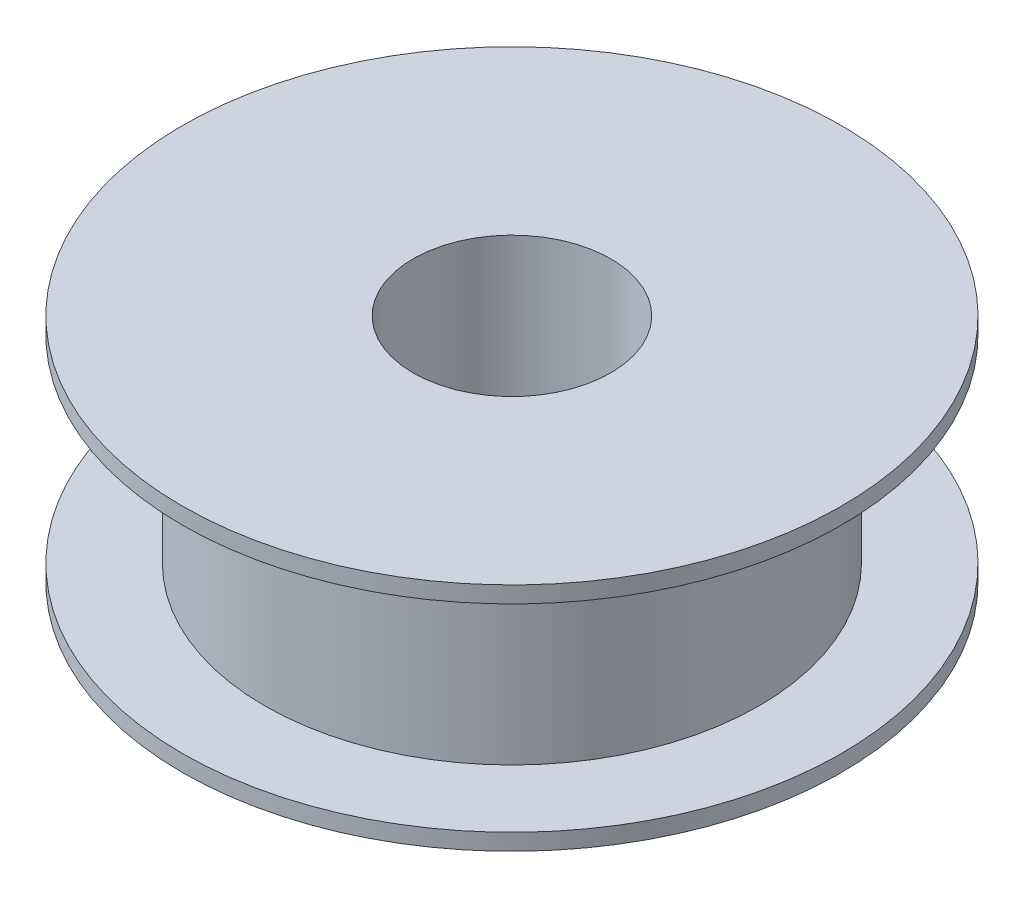
SolidWorks part; units mm, degrees
ref_plane "Plan de face" through (0, 0, 0) normal (0, 0, 1) x (1, 0, 0)
ref_plane "Plan de dessus" through (0, 0, 0) normal (0, 1, 0) x (1, 0, 0)
ref_plane "Plan de droite" through (0, 0, 0) normal (1, 0, 0) x (0, 0, -1)
sketch "Esquisse1" plane through (0, 0, 0) normal (0, 1, 0) x (1, 0, 0)
  circle A0 centre (0, 0) radius 15
  circle A1 centre (0, 0) radius 20
  circle A2 centre (0, 0) radius 6
  dimension "D1" = 5
  dimension "D2" = 30
  dimension "D3" = 12
extrude "Boss.-Extru.1" add sketch "Esquisse1" against normal blind 1 contours A1 A0 | A0 A2 region at (-14.5757, 0, 0) region at (-19.4343, 0, 0)
extrude "Boss.-Extru.2" add sketch "Esquisse1<3>" along normal blind 12 contours A0 A2 region at (-14.5757, 0, 0)
sketch "Esquisse1<3>" plane through (0, 0, 0) normal (0, 1, 0) x (1, 0, 0) same geometry as "Esquisse1"
sketch "Esquisse2" plane through (0, 12, 0) normal (0, 1, 0) x (1, 0, 0)
  circle A0 centre (0, 0) radius 20
  circle A1 centre (0, 0) radius 20 construction
  circle M1 centre (0, 0) radius 6
  circle M2 centre (0, 0) radius 15
extrude "Boss.-Extru.4" add sketch "Esquisse2" along normal blind 1 contours M2 M1 | A0 M2 region at (-19.4343, 12, 0) region at (-14.5757, 12, 0)
sketch3d "Esquisse3D2"
  line L0 (0, -1, 0) -> (0, 5.7948, 0) construction
  line L1 (0, -1, 0) -> (0, 13, 0) construction
  line L2 (0, 5.7948, 0) -> (0, 12.5897, 0) construction
  line L3 (0, 13, 0) -> (0, 12, 0) construction
  circle A0 centre (0, 13, 0) radius 6 construction
  point P9 (0, 7, 0)
